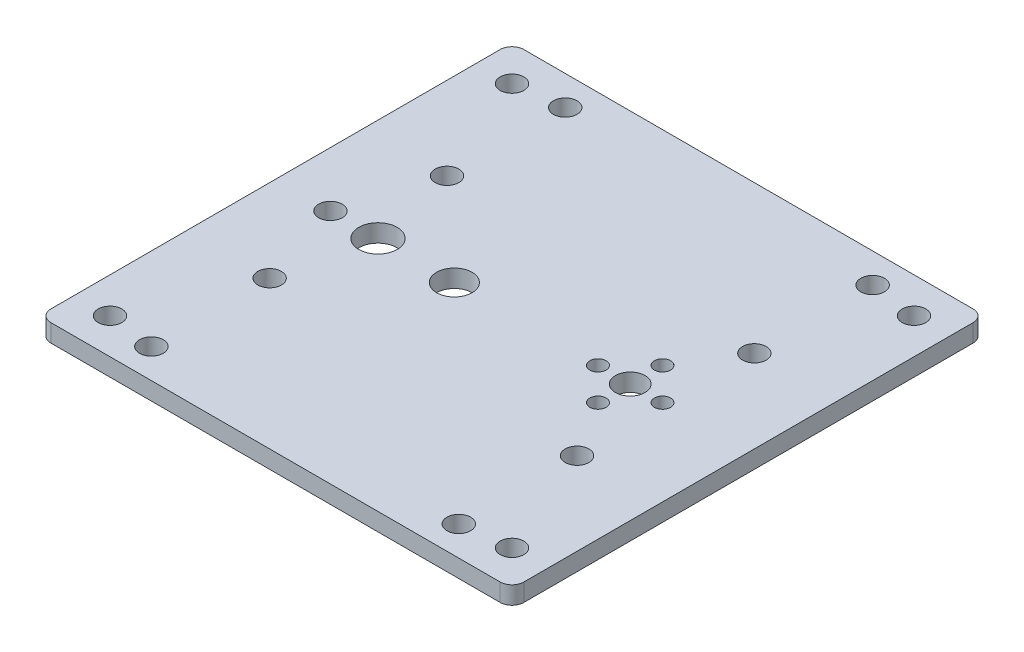
SolidWorks part; units mm, degrees
ref_plane "Front Plane" through (0, 0, 0) normal (0, 0, 1) x (1, 0, 0)
ref_plane "Top Plane" through (0, 0, 0) normal (0, 1, 0) x (1, 0, 0)
ref_plane "Right Plane" through (0, 0, 0) normal (1, 0, 0) x (0, 0, -1)
sketch "Sketch1" plane through (0, 0, 0) normal (0, 1, 0) x (1, 0, 0)
  line L1 (0, 0) -> (80, 0)
  line L2 (0, 0) -> (0, 80)
  line L3 (0, 80) -> (80, 80)
  line L4 (80, 0) -> (80, 80)
  dimension "D1" = 80
  dimension "D2" = 80
extrude "Boss-Extrude1" add sketch "Sketch1" along normal blind 3
sketch "Sketch2" plane through (0, 3, 0) normal (0, 1, 0) x (1, 0, 0)
  line L0 (0, 40) -> (80, 40) construction
  line L1 (0, 80) -> (0, 0) construction
  line L2 (80, 0) -> (80, 80) construction
  circle A0 centre (9.29, 40) radius 2
  circle A1 centre (17.33, 40) radius 3.25
  dimension "D2" = 4
  dimension "D4" = 6.5
  dimension "D1" = 9.29
  dimension "D3" = 8.04
extrude "Cut-Extrude1" cut sketch "Sketch2" against normal through all
sketch "Sketch3" plane through (0, 3, 0) normal (0, 1, 0) x (1, 0, 0)
  line L0 (0, 40) -> (80, 40) construction
  line L1 (0, 80) -> (0, 0) construction
  line L2 (80, 0) -> (80, 80) construction
  circle A0 centre (60, 40) radius 2.5
  dimension "D2" = 5
  dimension "D1" = 20
extrude "Cut-Extrude2" cut sketch "Sketch3" against normal through all
sketch "Sketch4" plane through (0, 3, 0) normal (0, 1, 0) x (1, 0, 0)
  line L0 (0, 40) -> (80, 40) construction
  line L1 (0, 80) -> (0, 0) construction
  line L2 (80, 0) -> (80, 80) construction
  line L3 (60, 40) -> (60, 0) construction
  line L4 (60, 40) -> (60, 80) construction
  line L5 (80, 80) -> (0, 80) construction
  circle A0 centre (65.46, 40) radius 1.375
  circle A1 centre (54.54, 40) radius 1.375
  circle A2 centre (60, 34.54) radius 1.375
  circle A3 centre (60, 45.46) radius 1.375
  dimension "D1" = 2.75
  dimension "D3" = 2.75
  dimension "D4" = 2.75
  dimension "D5" = 2.75
  dimension "D2" = 5.46
  dimension "D6" = 5.46
  dimension "D7" = 5.46
  dimension "D8" = 5.46
extrude "Cut-Extrude3" cut sketch "Sketch4" against normal through all
sketch "Sketch5" plane through (0, 3, 0) normal (0, 1, 0) x (1, 0, 0)
  line L0 (0, 40) -> (80, 40) construction
  line L1 (0, 80) -> (0, 0) construction
  line L2 (80, 0) -> (80, 80) construction
  circle A0 centre (30.25, 40) radius 3
  dimension "D2" = 6
  dimension "D1" = 30.25
extrude "Cut-Extrude4" cut sketch "Sketch5" against normal through all
sketch "Sketch6" plane through (0, 3, 0) normal (0, 1, 0) x (1, 0, 0)
  line L0 (40, 80) -> (40, 0) construction
  line L1 (80, 80) -> (0, 80) construction
  line L2 (0, 0) -> (80, 0) construction
  line L3 (0, 40) -> (80, 40) construction
  line L4 (0, 80) -> (0, 0) construction
  line L5 (80, 0) -> (80, 80) construction
  circle A0 centre (6, 74) radius 2
  circle A1 centre (74, 74) radius 2
  circle A2 centre (74, 6) radius 2
  circle A3 centre (6, 6) radius 2
  dimension "D3" = 4
  dimension "D1" = 6
  dimension "D2" = 6
extrude "Cut-Extrude5" cut sketch "Sketch6" against normal through all
fillet "Fillet1" radius 2 4 edges at (0, 1.5, -80) (80, 1.5, -80) (0, 1.5, 0) (80, 1.5, 0)
sketch "Sketch7" plane through (0, 3, 0) normal (0, 1, 0) x (1, 0, 0)
  line L0 (2, 0) -> (78, 0) construction
  line L1 (80, 2) -> (80, 78) construction
  line L2 (78, 80) -> (2, 80) construction
  line L6 (0, 78) -> (0, 2) construction
  circle A0 centre (14, 5) radius 2
  circle A1 centre (66, 5) radius 2
  circle A2 centre (66, 25) radius 2
  circle A3 centre (14, 25) radius 2
  circle A4 centre (14, 75) radius 2
  circle A5 centre (14, 55) radius 2
  circle A6 centre (66, 75) radius 2
  circle A7 centre (66, 55) radius 2
  dimension "D7" = 4
  dimension "D1" = 4
  dimension "D9" = 4
  dimension "D10" = 4
  dimension "D13" = 4
  dimension "D17" = 4
  dimension "D23" = 4
  dimension "D24" = 4
  dimension "D2" = 5
  dimension "D3" = 14
  dimension "D4" = 14
  dimension "D5" = 14
  dimension "D6" = 5
  dimension "D8" = 14
  dimension "D11" = 25
  dimension "D12" = 25
  dimension "D14" = 14
  dimension "D15" = 5
  dimension "D16" = 5
  dimension "D18" = 14
  dimension "D19" = 14
  dimension "D20" = 14
  dimension "D21" = 25
  dimension "D22" = 25
extrude "Cut-Extrude6" cut sketch "Sketch7" against normal through all
